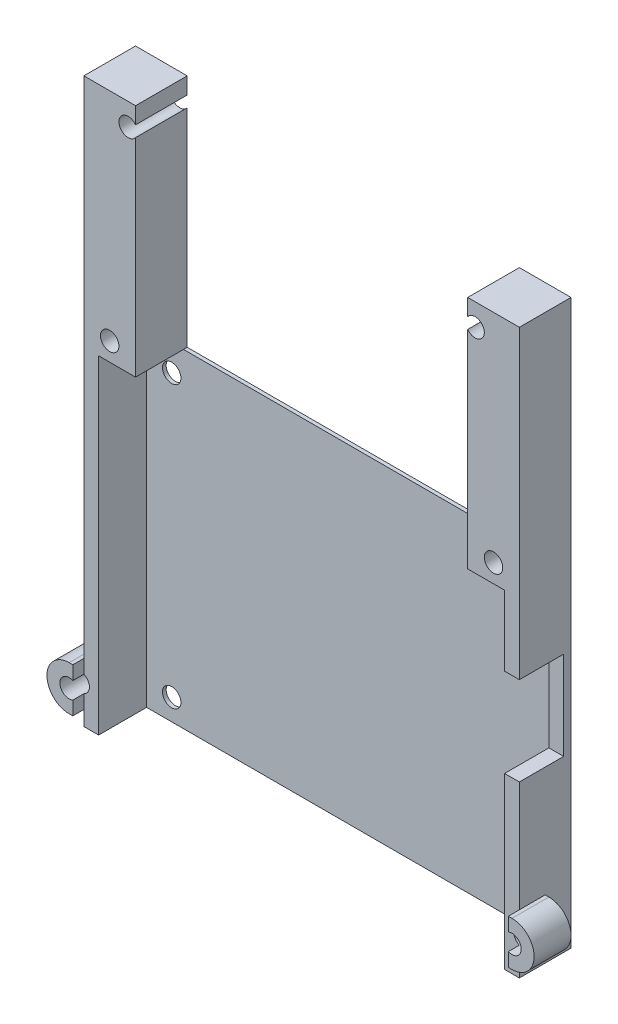
SolidWorks part; units mm, degrees
ref_plane "Front Plane" through (0, 0, 0) normal (0, 0, 1) x (1, 0, 0)
ref_plane "Top Plane" through (0, 0, 0) normal (0, 1, 0) x (1, 0, 0)
ref_plane "Right Plane" through (0, 0, 0) normal (1, 0, 0) x (0, 0, -1)
sketch "Sketch1" plane through (0, 0, 0) normal (0, 1, 0) x (1, 0, 0)
  line L0 (0, 0) -> (2, 0)
  line L1 (0, 0) -> (59, 0) construction
  line L2 (0, 0) -> (0, 7)
  line L3 (0, 7) -> (59, 7)
  line L4 (59, 0) -> (59, 7)
  line L5 (2, 0) -> (2, 6.5)
  line L6 (2, 6.5) -> (57, 6.5)
  line L7 (57, 6.5) -> (57, 0)
  line L8 (57, 0) -> (59, 0)
  dimension "D1" = 59
  dimension "D2" = 7
  dimension "D3" = 2
  dimension "D4" = 6.5
  dimension "D5" = 55
extrude "Boss-Extrude1" add sketch "Sketch1" along normal blind 44.5
sketch "Sketch2" plane through (59, 0, 0) normal (1, 0, 0) x (0, 0, -1)
  line L0 (0, 0) -> (0, 23) construction
  line L1 (0, 44.5) -> (0, 0) construction
  line L2 (0, 23) -> (6, 23)
  line L3 (6, 23) -> (6, 35)
  line L4 (6, 35) -> (0, 35)
  line L5 (0, 35) -> (0, 23)
  dimension "D1" = 23
  dimension "D2" = 6
  dimension "D3" = 12
extrude "Cut-Extrude1" cut sketch "Sketch2" against normal blind 10
sketch "Sketch3" plane through (0, 0, -7) normal (0, 0, -1) x (-1, 0, 0)
  line L0 (-59, 0) -> (-59, 8) construction
  line L1 (-59, 44.5) -> (-59, 0) construction
  line L2 (-59, 8) -> (-59, 2)
  line L3 (-59, 5) -> (-59.5, 5) construction
  line L4 (-59, 8) -> (-59.5, 8)
  line L5 (-59, 2) -> (-59.5, 2)
  line L6 (0, 0) -> (0, 8) construction
  line L7 (0, 44.5) -> (0, 0) construction
  line L8 (0, 8) -> (0.5, 8)
  line L9 (0, 8) -> (0, 2)
  line L10 (0, 2) -> (0.5, 2)
  line L11 (0, 5) -> (0.5, 5) construction
  arc A0 (-59.5, 8) -> (-59.5, 2) centre (-59.5, 5) ccw
  circle A1 centre (-59.5, 5) radius 1.25
  arc A2 (0.5, 8) -> (0.5, 2) centre (0.5, 5) cw
  circle A3 centre (0.5, 5) radius 1.25
  line M5 (0, 0) -> (0, 44.5)
  line M7 (-59, 44.5) -> (-59, 0)
  dimension "D4" = 3
  dimension "D5" = 2.5
  dimension "D11" = 3
  dimension "D12" = 2.5
  dimension "D1" = 8
  dimension "D2" = 6
  dimension "D3" = 0.5
  dimension "D6" = 8
  dimension "D7" = 0.5
  dimension "D8" = 6
  dimension "D9" = 0.5
extrude "Boss-Extrude2" add sketch "Sketch3" against normal blind 8.5 contours A1 L4 A0 L5 M7 | A3 L10 A2 L8 M5 region at (59.0695, 7.0728, -7) region at (-0.25, 7.9305, -7)
extrude "Cut-Extrude2" cut sketch "Sketch3<3>" against normal blind 11 contours L2 A1 | L9 A3 region at (58.6906, 5, -7) region at (0.3094, 5, -7)
sketch "Sketch3<3>" plane through (0, 0, -7) normal (0, 0, -1) x (-1, 0, 0) same geometry as "Sketch3"
sketch "Sketch4" plane through (0, 44.5, 0) normal (0, 1, 0) x (1, 0, 0)
  line L0 (59, 7) -> (0, 7) construction
  line L1 (0, 0) -> (7, 0)
  line L2 (0, 0) -> (0, 7)
  line L3 (0, 7) -> (7, 7)
  line L4 (7, 0) -> (7, 7)
  line L6 (59, 0) -> (52, 0)
  line L7 (59, 0) -> (59, 7)
  line L8 (59, 7) -> (52, 7)
  line L9 (52, 0) -> (52, 7)
  dimension "D1" = 7
  dimension "D2" = 7
extrude "Boss-Extrude3" add sketch "Sketch4" along normal blind 5
sketch "Sketch9" plane through (0, 49.5, 0) normal (0, 1, 0) x (1, 0, 0)
  line L1 (0, 0) -> (7, 0)
  line L2 (0, 0) -> (0, 7)
  line L3 (0, 7) -> (7, 7)
  line L4 (7, 0) -> (7, 7)
  line L5 (52, 0) -> (59, 0)
  line L6 (52, 0) -> (52, 7)
  line L7 (52, 7) -> (59, 7)
  line L8 (59, 0) -> (59, 7)
extrude "Boss-Extrude5" add sketch "Sketch9" along normal blind 26.85
sketch "Sketch5" plane through (0, 0, -7) normal (0, 0, -1) x (-1, 0, 0)
  line L0 (-59, 49.5) -> (-52, 44.5) construction
  line L1 (0, 49.5) -> (-7, 44.5) construction
  line L2 (-53, 73.35) -> (-6, 73.35) construction
  line L3 (-6, 73.35) -> (-6, 47) construction
  line L4 (-6, 47) -> (-3.5, 47) construction
  circle A0 centre (-55.5, 47) radius 1.25
  circle A1 centre (-3.5, 47) radius 1.25
  circle A2 centre (-6, 73.35) radius 1.25
  circle A3 centre (-53, 73.35) radius 1.25
  point P18 (-6, 73.35)
  dimension "D1" = 2.5
  dimension "D2" = 2.5
extrude "Cut-Extrude3" cut sketch "Sketch5" against normal through all
sketch "Sketch7" plane through (0, 0, -7) normal (0, 0, -1) x (-1, 0, 0)
  line L0 (-59, 0) -> (-59, 2.9) construction
  line L1 (-59, 2) -> (-59, 0) construction
  line L2 (-59, 2.9) -> (0, 2.9) construction
  line L3 (0, 2) -> (0, 0) construction
  line L4 (-53.6, 2.9) -> (-5.4, 2.9)
  line L5 (-53.6, 2.9) -> (-53.6, 40.95) construction
  line L6 (-53.6, 40.95) -> (-5.4, 40.95) construction
  circle A0 centre (-53.6, 2.9) radius 1.25
  circle A1 centre (-5.4, 2.9) radius 1.25
  circle A2 centre (-53.6, 40.95) radius 1.25
  circle A3 centre (-5.4, 40.95) radius 1.25
  point P11 (-29.5, 2.9)
  dimension "D3" = 2.5
  dimension "D4" = 2.5
  dimension "D6" = 2.5
  dimension "D8" = 2.5
  dimension "D1" = 2.9
  dimension "D2" = 48.2
  dimension "D5" = 38.05
  dimension "D7" = 48.2
extrude "Cut-Extrude4" cut sketch "Sketch7" against normal blind 10 contours A2 | A3 | A1 | A0 region at (5.4, 4.1146, -7) region at (54.8146, 2.9, -7) region at (53.6, 40.95, -7) region at (5.4, 40.95, -7)
extrude "Cut-Extrude6" cut sketch "Sketch3<4>" against normal blind 3.5 contours A1 L4 A0 L5 M7 | A3 L10 A2 L8 M5 region at (59.0695, 7.0728, -7) region at (-0.25, 7.9305, -7)
sketch "Sketch3<4>" plane through (0, 0, -7) normal (0, 0, -1) x (-1, 0, 0) same geometry as "Sketch3"
extrude "Boss-Extrude4" add sketch "Sketch3<5>" against normal blind 3 contours L9 A3 | L2 A1 region at (58.6906, 5, -7) region at (0.3094, 5, -7)
sketch "Sketch3<5>" plane through (0, 0, -7) normal (0, 0, -1) x (-1, 0, 0) same geometry as "Sketch3"
